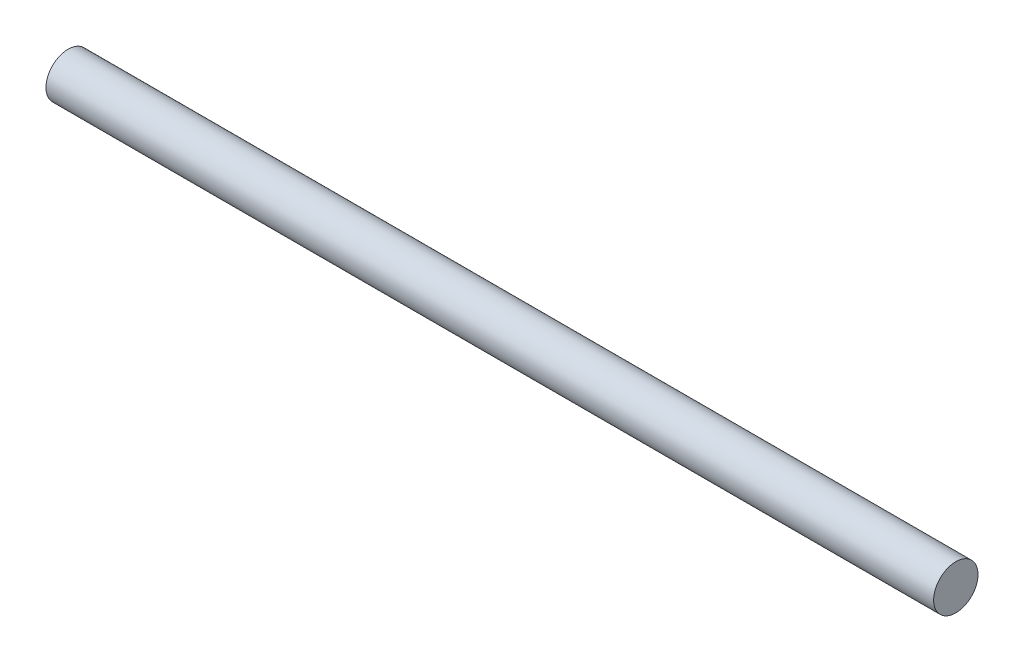
SolidWorks part; units mm, degrees
ref_plane "Front Plane" through (0, 0, 0) normal (0, 0, 1) x (1, 0, 0)
ref_plane "Top Plane" through (0, 0, 0) normal (0, 1, 0) x (1, 0, 0)
ref_plane "Right Plane" through (0, 0, 0) normal (1, 0, 0) x (0, 0, -1)
sketch "Sketch1" plane through (0, 0, 0) normal (1, 0, 0) x (0, 0, -1)
  circle A0 centre (0, 0) radius 3
  dimension "D1" = 6
extrude "Boss-Extrude1" add sketch "Sketch1" along normal blind 120
